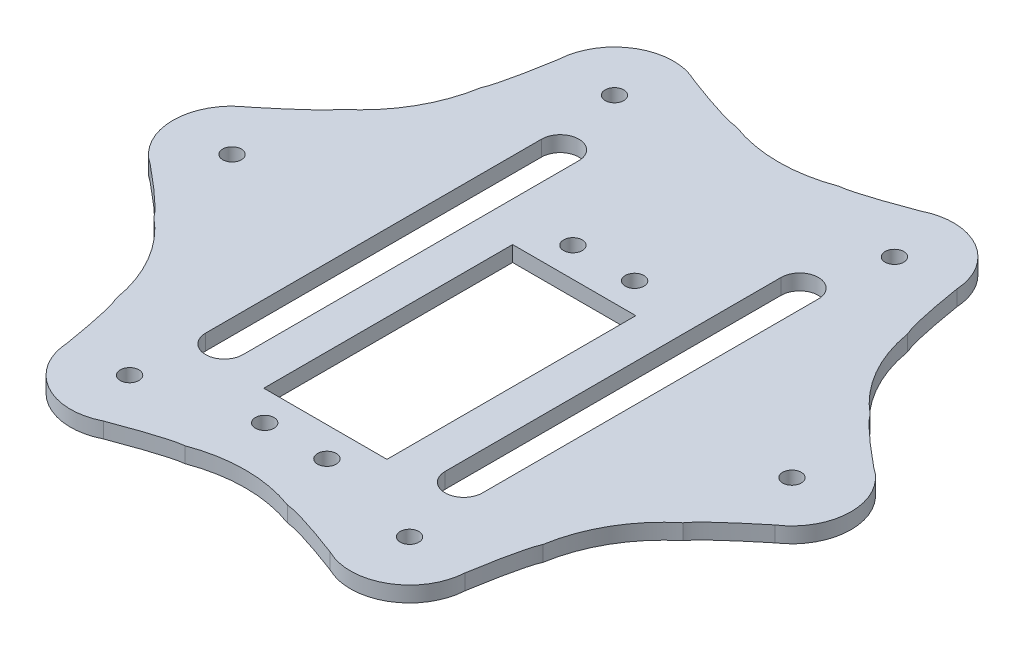
SolidWorks part; units mm, degrees
material "ABS"
ref_plane "Front" through (0, 0, 0) normal (0, 0, 1) x (1, 0, 0)
ref_plane "Top" through (0, 0, 0) normal (0, 1, 0) x (1, 0, 0)
ref_plane "Right" through (0, 0, 0) normal (1, 0, 0) x (0, 0, -1)
sketch "Sketch1" plane through (0, 0, 0) normal (0, 1, 0) x (1, 0, 0)
  line L0 (0, 45) -> (0, -45) construction
  line L1 (-45, 0) -> (45, 0) construction
  line L2 (-9.9, -30) -> (-9.9, 0)
  line L3 (9.9, -30) -> (9.9, 0)
  line L4 (-9.9, 0) -> (-9.9, 10)
  line L5 (-9.9, -30) -> (9.9, -30)
  line L6 (-22.25, 27) -> (-22.25, -27)
  line L7 (-16.25, 27) -> (-16.25, -27)
  line L8 (16.25, 27) -> (16.25, -27)
  line L9 (22.25, 27) -> (22.25, -27)
  line L10 (0, 45) -> (0, 37.5) construction
  line L11 (9.9, 0) -> (9.9, 10)
  line L12 (-9.9, 10) -> (9.9, 10)
  line L16 (-4.955, 14.75) -> (-5, -34.75) construction
  line L18 (0, 6.1303) -> (0, -27.7397) construction
  circle A0 centre (0, 0) radius 45
  arc A1 (-22.25, 27) -> (-16.25, 27) centre (-19.25, 27) cw
  arc A2 (-22.25, -27) -> (-16.25, -27) centre (-19.25, -27) ccw
  arc A3 (22.25, -27) -> (16.25, -27) centre (19.25, -27) cw
  arc A4 (22.25, 27) -> (16.25, 27) centre (19.25, 27) ccw
  circle A5 centre (-5, -34.75) radius 1.5
  circle A6 centre (5, -34.75) radius 1.5
  circle A7 centre (-4.955, 14.75) radius 1.5
  circle A8 centre (4.955, 14.75) radius 1.5
  point P11 (0, 24.3484)
  point P13 (9.9, 0)
  point P14 (-9.9, 0)
  point P18 (-22.25, 0)
  point P28 (22.25, 0)
  point P30 (0, 0)
  point P40 (0, 0)
  point P41 (0, 0)
  dimension "D3" = 3
  dimension "D5" = 9.91
  dimension "D6" = 90
  dimension "D7" = 19.8
  dimension "D9" = 10
  dimension "D10" = 3
  dimension "D1" = 30
  dimension "D2" = 10
  dimension "D4" = 49.5
  dimension "D8" = 34.75
  dimension "D11" = 19.25
  dimension "D12" = 24.3484
extrude "Boss-Extrude2" add sketch "Sketch1" along normal blind 2.5
ref_plane "Plane1" through (0, 2.5, 0) normal (0, 1, 0) x (1, 0, 0)
sketch "Sketch2" plane through (0, 2.5, 0) normal (0, 1, 0) x (1, 0, 0)
  line L0 (0, 45) -> (0, -45) construction
  line L1 (-45, 0) -> (45, 0) construction
  line L2 (-54.5, 0) -> (-35.5, 0) construction
  line L4 (-51.7175, -6.7175) -> (-45, 0) construction
  circle A0 centre (0, 0) radius 45 construction
  arc A2 (-42.2345, 15.532) -> (-42.2345, -15.532) centre (0, 0) ccw
  arc A3 (-50.2124, 7.9424) -> (-50.2124, -7.9424) centre (-45, 0) ccw
  spline S0 degree 3 poles (-50.2124, -7.9424) (-45.316, -11.9596) (-42.6567, -14.4895) (-42.2345, -15.532) knots 0.089312 0.089312 0.089312 0.089312 1 1 1 1
  spline S1 degree 3 poles (-50.2124, 7.9424) (-45.316, 11.9596) (-42.6567, 14.4895) (-42.2345, 15.532) knots 0.089312 0.089312 0.089312 0.089312 1 1 1 1
  dimension "D2" = 45
extrude "Boss-Extrude4" add sketch "Sketch2" against normal up to surface (2.5 mm away) up to face at (-19.25, 0, 0)
pattern_circular "CirPattern1" count 6 over 360 about axis through (0, 2.5, 0) along (0, 1, 0) of "Boss-Extrude4"
ref_plane "Plane2" through (0, 2.5, 0) normal (0, 1, 0) x (1, 0, 0)
sketch "Sketch5" plane through (0, 2.5, 0) normal (0, 1, 0) x (1, 0, 0)
  line L0 (0, 45) -> (0, -45) construction
  line L1 (-8.2247, 44.3422) -> (0, 46.6578)
  line L2 (0, 46.6578) -> (8.2247, 44.3422)
  line L3 (40.4069, 23.3289) -> (42.5138, 15.0483)
  line L4 (34.2891, 29.2939) -> (40.4069, 23.3289)
  line L5 (40.4069, -23.3289) -> (34.2891, -29.2939)
  line L6 (42.5138, -15.0483) -> (40.4069, -23.3289)
  line L7 (0, -46.6578) -> (-8.2247, -44.3422)
  line L8 (8.2247, -44.3422) -> (0, -46.6578)
  line L9 (-40.4069, -23.3289) -> (-42.5138, -15.0483)
  line L10 (-34.2891, -29.2939) -> (-40.4069, -23.3289)
  line L11 (-40.4069, 23.3289) -> (-34.2891, 29.2939)
  line L12 (-42.5138, 15.0483) -> (-40.4069, 23.3289)
  arc A0 (7.6662, 44.3422) -> (-7.6662, 44.3422) centre (0, 0) ccw construction
  arc A1 (-7.6662, -44.3422) -> (7.6662, -44.3422) centre (0, 0) ccw construction
  arc A2 (-8.2247, 44.3422) -> (8.2247, 44.3422) centre (0, 66.2885) ccw
  arc A3 (34.2891, 29.2939) -> (42.5138, 15.0483) centre (57.4076, 33.1443) ccw
  arc A4 (42.5138, -15.0483) -> (34.2891, -29.2939) centre (57.4076, -33.1443) ccw
  arc A5 (8.2247, -44.3422) -> (-8.2247, -44.3422) centre (0, -66.2885) ccw
  arc A6 (-34.2891, -29.2939) -> (-42.5138, -15.0483) centre (-57.4076, -33.1443) ccw
  arc A7 (-42.5138, 15.0483) -> (-34.2891, 29.2939) centre (-57.4076, 33.1443) ccw
  parabola Q0 (-7.6662, 44.3422) -> (-18.2279, 47.4564) focus (-7.4049, 44.5798) apex (-7.3043, 44.5299) construction
  parabola Q1 (18.2279, 47.4564) -> (7.6662, 44.3422) focus (7.4049, 44.5798) apex (7.3043, 44.5299) construction
  point P42 (0, 0)
  dimension "D1" = 6
extrude "Cut-Extrude2" cut sketch "Sketch5" against normal blind 2.5
ref_plane "Plane3" through (0, 2.5, 0) normal (0, 1, 0) x (1, 0, 0)
sketch "Sketch6" plane through (0, 2.5, 0) normal (0, 1, 0) x (1, 0, 0)
  line L0 (0, 42.8517) -> (0, -42.8517) construction
  circle A0 centre (-45, 0) radius 1.5
  arc A1 (-8.2247, 44.3422) -> (8.2247, 44.3422) centre (0, 66.2885) ccw construction
  arc A2 (8.2247, -44.3422) -> (-8.2247, -44.3422) centre (0, -66.2885) ccw construction
  circle A7 centre (-22.5, 38.9711) radius 1.5
  circle A8 centre (22.5, 38.9711) radius 1.5
  circle A9 centre (45, 0) radius 1.5
  circle A10 centre (22.5, -38.9711) radius 1.5
  circle A11 centre (-22.5, -38.9711) radius 1.5
  point P37 (0, 0)
  dimension "D4" = 3
  dimension "D5" = 22.5
  dimension "D3" = 6
extrude "Cut-Extrude3" cut sketch "Sketch6" against normal mid plane 10
